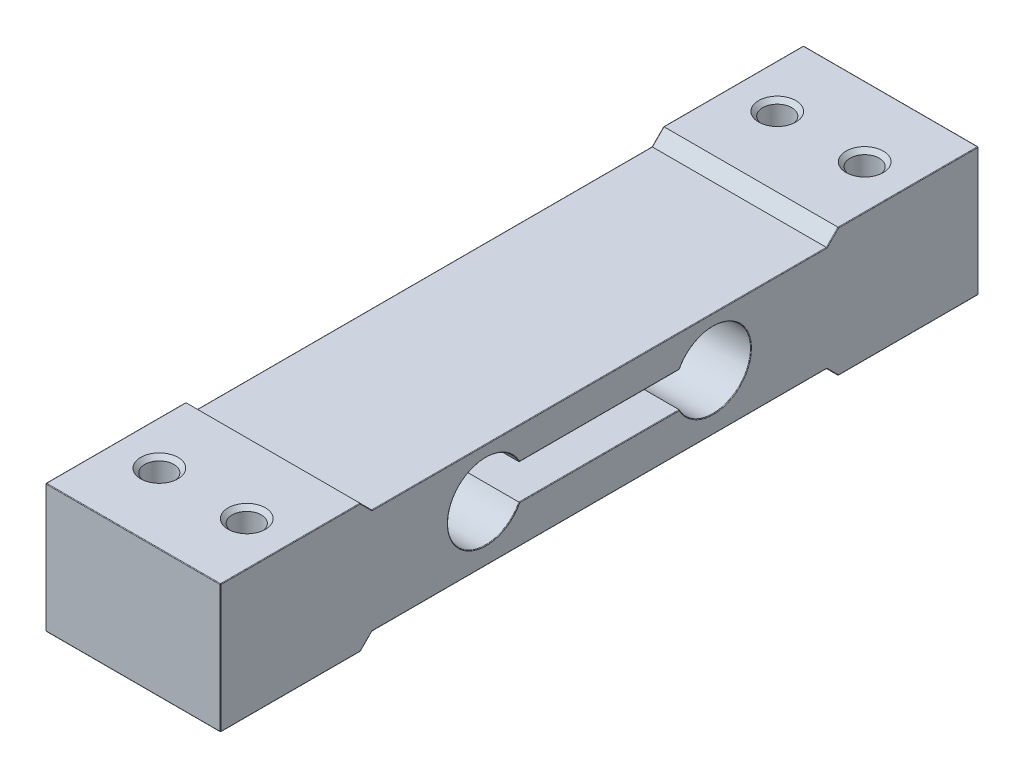
SolidWorks part; units mm, degrees
ref_plane "Front Plane" through (0, 0, 0) normal (0, 0, 1) x (1, 0, 0)
ref_plane "Top Plane" through (0, 0, 0) normal (0, 1, 0) x (1, 0, 0)
ref_plane "Right Plane" through (0, 0, 0) normal (1, 0, 0) x (0, 0, -1)
sketch "Эскиз1" plane through (0, 0, 0) normal (1, 0, 0) x (0, 0, -1)
  line L0 (24, 22) -> (26, 20)
  line L1 (106, 0) -> (130, 0)
  line L2 (0, 0) -> (0, 22)
  line L3 (0, 22) -> (24, 22)
  line L4 (130, 0) -> (130, 22)
  line L5 (26, 20) -> (104, 20)
  line L6 (104, 20) -> (106, 22)
  line L7 (106, 22) -> (130, 22)
  line L8 (0, 11) -> (143.2604, 11) construction
  line L9 (104, 2) -> (106, 0)
  line L10 (26, 2) -> (104, 2)
  line L11 (0, 0) -> (24, 0)
  line L12 (24, 0) -> (26, 2)
  point P14 (130, 11)
  dimension "D3" = 24
  dimension "D4" = 24
  dimension "D5" = 45
  dimension "D6" = 45
  dimension "D7" = 2
extrude "Бобышка-Вытянуть1" add sketch "Эскиз1" along normal blind 15 and the other way blind 15
sketch "Эскиз2" plane through (15, 0, 0) normal (1, 0, 0) x (0, 0, -1)
  line L0 (91, -11.6364) -> (91, 32.8489) construction
  line L1 (39, 31.9285) -> (39, -14.2442) construction
  line L2 (51.2663, 14.5266) -> (78.7337, 14.5266)
  line L3 (45.5, 11.5266) -> (84.5, 11.5266) construction
  line L4 (51.2663, 8.5266) -> (78.7337, 8.5266)
  arc A0 (78.7337, 8.5266) -> (78.7337, 14.5266) centre (84.5, 11.5266) ccw
  arc A1 (51.2663, 14.5266) -> (51.2663, 8.5266) centre (45.5, 11.5266) ccw
  dimension "D1" = 15
  dimension "D4" = 13
  dimension "D2" = 15
  dimension "D3" = 3
extrude "Вырез-Вытянуть1" cut sketch "Эскиз2" against normal blind 45
sketch "Эскиз12" plane through (0, 0, 0) normal (0, -1, 0) x (1, 0, 0)
  line L0 (-15, -130) -> (15, -130) construction
  line L1 (7.5, -118) -> (-7.5, -118) construction
  line L2 (-7.5, -118) -> (-7.5, -12) construction
  line L3 (-7.5, -12) -> (7.5, -12) construction
  line L4 (7.5, -12) -> (7.5, -118) construction
  line L6 (0, -12.1) -> (0, 12.1) construction
  circle A0 centre (7.5, -118) radius 2.5
  circle A1 centre (-7.5, -118) radius 2.5
  circle A2 centre (7.5, -12) radius 2.5
  circle A3 centre (-7.5, -12) radius 2.5
  dimension "D1" = 12
  dimension "D2" = 106
  dimension "D3" = 15
  dimension "D4" = 7.5
  dimension "D5" = 5
extrude "Вырез-Вытянуть2" cut sketch "Эскиз12" against normal blind 40
chamfer "Фаска1" distance 0.7 angle 45 8 edges at (-7.5, 0, -120.5) (-7.5, 22, -115.5) (7.5, 0, -120.5) (7.5, 22, -115.5) (7.5, 0, -14.5) (7.5, 22, -9.5) (-7.5, 0, -14.5) (-7.5, 22, -9.5)
fillet "Скругление1" radius 0.1 36 edges at (-15, 0, -118) (-15, 22, -118) (-15, 21, -105) (-15, 20, -65) (-15, 21, -25) (-15, 22, -12) (-15, 0, -12) (-15, 1, -25) (-15, 2, -65) (-15, 1, -105) (-15, 11.5266, -39) (-15, 14.5266, -65) (-15, 11.5266, -91) (-15, 8.5266, -65) (-15, 11, -130) (0, 0, -130) (0, 22, -130) (-15, 11, 0) (0, 22, 0) (0, 0, 0) (15, 2, -65) (15, 1, -25) (15, 0, -12) (15, 11, 0) (15, 22, -12) (15, 21, -25) (15, 20, -65) (15, 21, -105) (15, 22, -118) (15, 11, -130) (15, 0, -118) (15, 1, -105) (15, 14.5266, -65) (15, 11.5266, -39) (15, 8.5266, -65) (15, 11.5266, -91)
sketch "Эскиз13" plane through (-15, 0, 0) normal (-1, 0, 0) x (0, 0, 1)
  line L0 (-129.9, 21.9) -> (-129.9, 0.1) construction
  line L1 (-129.9, 22) -> (-106, 22) construction
  circle A0 centre (-123.9, 11) radius 1.75
  point P4 (-129.9, 11)
  dimension "D1" = 3.5
  dimension "D2" = 6
  dimension "D3" = 11
extrude "Вырез-Вытянуть3" cut sketch "Эскиз13" against normal blind 10
sketch "Эскиз15" plane through (-5, 0, 0) normal (-1, 0, 0) x (0, 0, 1)
  circle A0 centre (-123.9, 11) radius 1.75
extrude "Бобышка-Вытянуть2" add sketch "Эскиз15" along normal blind 15 separate body
